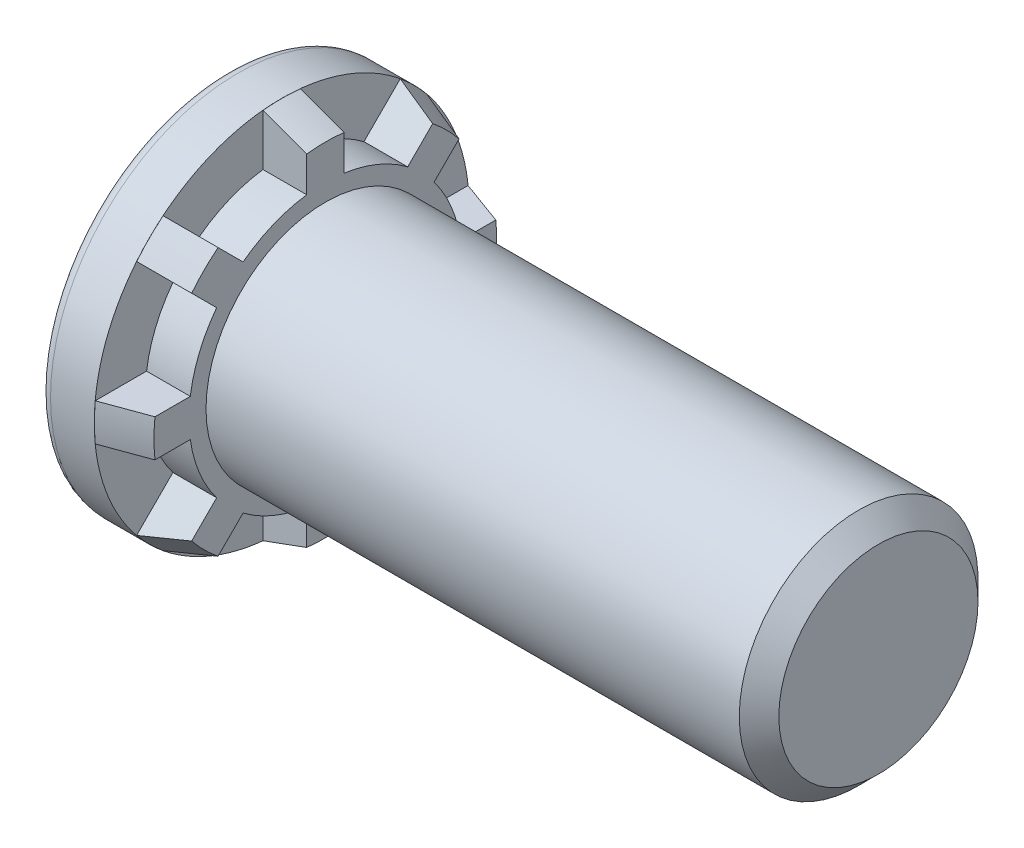
SolidWorks part; units mm, degrees
revolve "BaseBody" add sketch "BodySke" angle 360 about L6 other way angle 7.5
sketch "BodySke" plane through (0, 0, 0) normal (0, 0, 1) x (1, 0, 0)
  line L0 (-2.29, 7.392) -> (-2.29, 0)
  line L1 (1.832, 7.1816) -> (1.832, 5)
  line L2 (0.0025, 7.8475) -> (1.832, 7.1816)
  line L3 (1.832, 5) -> (24.172, 5)
  line L4 (25, 4.172) -> (25, 0)
  line L5 (25, 0) -> (-2.29, 0)
  line L6 (0, 0) -> (50.554, 0) construction
  line L8 (25, 4.172) -> (24.172, 5)
  line L9 (-1.832, 7.85) -> (0, 7.85)
  line L10 (0.0025, 7.8475) -> (0, 7.8475)
  line L11 (1.5, 19.05) -> (1.5, -3.175) construction
  line L12 (0, 7.8475) -> (0, 7.85)
  arc A0 (-2.29, 7.392) -> (-1.832, 7.85) centre (-1.832, 7.392) cw
  dimension "Fillet_rad" = 0.458
  dimension "Minor_dia" = 8.344
  dimension "Diameter" = 10
  dimension "T_dim" = 2.29
  dimension "H_dia" = 15.7
  dimension "D2" = 0.0025
  dimension "D3" = 0.0025
  dimension "Length" = 25
  dimension "Advance" = 1.5
  dimension "D1" = 20
cosmetic thread "ThreadCosmetic" [suppressed] parameters "Thread_length"=20.9, "Thread_minor"=8.344
ref_plane "Plane1" through (0, 0, 0) normal (0, 0, 1) x (1, 0, 0)
ref_plane "Plane2" through (0, 0, 0) normal (0, 1, 0) x (1, 0, 0)
ref_plane "Plane3" through (0, 0, 0) normal (1, 0, 0) x (0, 0, -1)
sketch "ThdSchSke" plane through (0, 0, 0) normal (0, 0, 1) x (1, 0, 0)
  line L0 (4.1, -4.172) -> (3.5202, -5)
  line L1 (4.1, -4.172) -> (4.6798, -5)
  line L2 (4.6798, -5) -> (4.6798, -6.25)
  line L3 (-3.175, 0) -> (5.1513, 0) construction
  line L4 (0, -7.85) -> (0, 7.85) construction
  line L5 (4.6798, -6.25) -> (3.5202, -6.25)
  line L6 (3.5202, -6.25) -> (3.5202, -5)
  dimension "Diameter" = 10
  dimension "Thread_minor" = 8.344
  dimension "Start" = 4.1
revolve "ThreadSchematic" [suppressed] cut sketch "ThdSchSke" angle 360 about L3
pattern_linear "ThdSchPat" [suppressed]
sketch "RibCutSke" plane through (1.832, 1.7944, -0.091) normal (1, 0, 0) x (0, 0, -1)
  line L0 (0.6912, 3.8643) -> (0.6912, 6.0165)
  line L1 (3.3573, 2.76) -> (4.8791, 4.2818)
  line L2 (0.6912, 3.144) -> (0.6912, 2.4006) construction
  line L3 (-0.091, -1.7944) -> (-0.091, 5.0239) construction
  line L4 (-0.091, -1.7944) -> (0.6912, 3.144) construction
  line L5 (-0.091, -1.7944) -> (2.848, 2.2507) construction
  line L6 (2.848, 2.2507) -> (2.3273, 1.73) construction
  arc A1 (3.3573, 2.76) -> (0.6912, 3.8643) centre (-0.091, -1.7944) ccw
  arc A2 (4.8791, 4.2818) -> (0.6912, 6.0165) centre (-0.091, -1.7944) ccw
  circle A3 centre (-0.091, -1.7944) radius 7.1816 construction
  circle A4 centre (-0.091, -1.7944) radius 5 construction
  dimension "Rib_root_half_angle" = 9
  dimension "Rib_root_gap_angle" = 27
  dimension "Angle" = 45
extrude "RibCut" cut sketch "RibCutSke" against normal blind 1.832
pattern_circular "RibCutsPat" count 8 every 45 about axis through (0, 0, 0) along (1, 0, 0) of "RibCut"
equation "' \"Length@BodySke\" = 25"
equation "' \"H_dia@BodySke\" = 15.7"
equation "' \"Start@ThdSchSke\" = 4.1"
equation "' \"T_dim@BodySke\" = 2.29"
equation "' \"Diameter@BodySke\" = 10"
equation "' \"Minor_dia@BodySke\" = 8.344"
equation "' \"Advance@BodySke\" = 1.5"
equation "\"Fillet_rad@BodySke\" =  \"T_dim@BodySke\" * 0.2"
equation "\"Clinch_ht@BodySke\" = \"T_dim@BodySke\" * 0.8"
equation "\"Num_ribs@RibCutsPat\" = 8"
equation "\"Angle@RibCutSke\" =\"Angle@RibCutsPat\""
equation "\"Rib_root_half_angle@RibCutSke\" = \"Angle@RibCutSke\" / 5"
equation "\"Rib_root_gap_angle@RibCutSke\" = \"Angle@RibCutSke\" - (2 * \"Rib_root_half_angle@RibCutSke\" )"
equation "\"Rib_root_dia@RibCutSke\" = \"Diameter@BodySke\""
equation "\"Inner_dia@RibCutSke\" = \"Diameter@BodySke\" + ( \"H_dia@BodySke\" - \"Diameter@BodySke\" ) / 4"
equation "\"Outer_dia@RibCutSke\" = \"H_dia@BodySke\""
equation "\"Depth@RibCut\" = \"Clinch_ht@BodySke\""
equation "\"Thread_length@ThreadCosmetic\" = \"Length@BodySke\" - \"Start@ThdSchSke\""
equation "\"Thread_minor@ThreadCosmetic\" = \"Minor_dia@BodySke\""
equation "\"Thread_minor@ThdSchSke\" = \"Minor_dia@BodySke\""
equation "\"Diameter@ThdSchSke\" = \"Diameter@BodySke\""
equation "\"Overcut@ThdSchSke\" = \"Diameter@BodySke\" * 1.25"
equation "\"Num_threads@ThdSchPat\" = int( \"Thread_length@ThreadCosmetic\" / \"Advance@BodySke\" + 0.999 )  + 1"
equation "\"Advance@ThdSchPat\" = \"Thread_length@ThreadCosmetic\" /  (\"Num_threads@ThdSchPat\" - 1) 'relax it"
equation "\"Num_threads@ThdSchPat\" = \"Num_threads@ThdSchPat\" - sgn( \"Num_threads@ThdSchPat\" - 1) '---chamfered tips only---"
